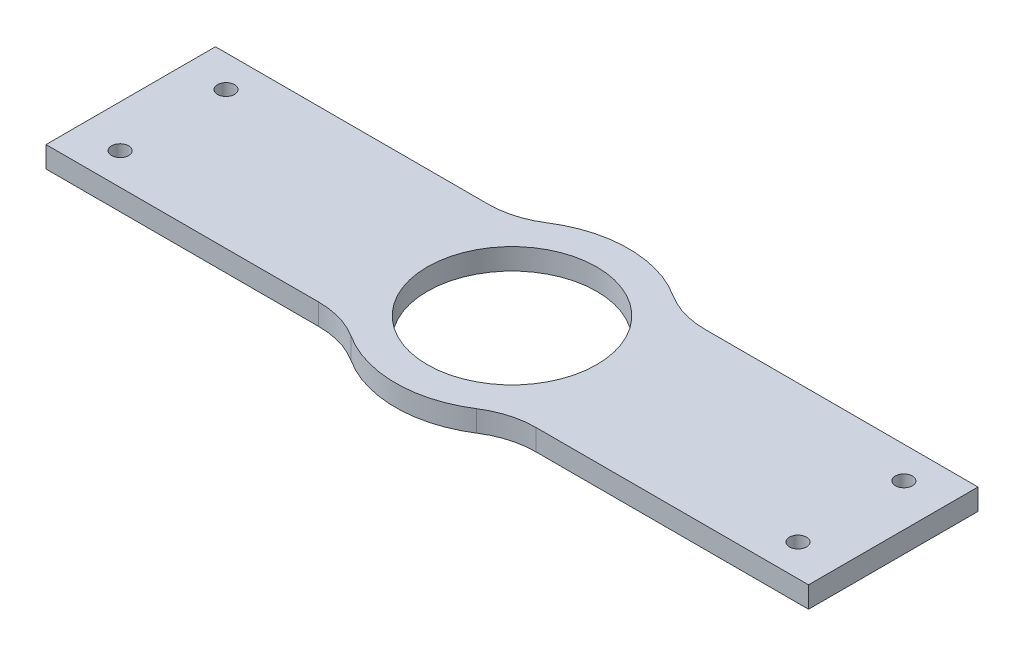
SolidWorks part; units mm, degrees
material "6061-T6 (SS)"
ref_plane "Front" through (0, 0, 0) normal (0, 0, 1) x (1, 0, 0)
ref_plane "Top" through (0, 0, 0) normal (0, 1, 0) x (1, 0, 0)
ref_plane "Right" through (0, 0, 0) normal (1, 0, 0) x (0, 0, -1)
sketch "Sketch1" plane through (0, 0, 0) normal (0, 1, 0) x (1, 0, 0)
  line L0 (228.6, 0) -> (228.6, 19.05) construction
  line L1 (0, 0) -> (81.7659, 0)
  line L2 (0, 0) -> (0, 50.8)
  line L3 (0, 50.8) -> (81.7659, 50.8)
  line L4 (228.6, 0) -> (228.6, 50.8)
  line L5 (0, 50.8) -> (228.6, 0) construction
  line L6 (146.8341, 50.8) -> (228.6, 50.8)
  line L7 (146.8341, 0) -> (228.6, 0)
  arc A0 (95.4645, -4.0105) -> (133.1355, -4.0105) centre (114.3, 25.4) ccw
  arc A1 (133.1355, 54.8105) -> (95.4645, 54.8105) centre (114.3, 25.4) ccw
  arc A2 (81.7659, 0) -> (95.4645, -4.0105) centre (81.7659, -25.4) cw
  arc A3 (146.8341, 0) -> (133.1355, -4.0105) centre (146.8341, -25.4) ccw
  arc A4 (146.8341, 50.8) -> (133.1355, 54.8105) centre (146.8341, 76.2) cw
  arc A5 (81.7659, 50.8) -> (95.4645, 54.8105) centre (81.7659, 76.2) ccw
  point P18 (138.2707, 50.8)
  dimension "D2" = 69.85
  dimension "D3" = 25.4
  dimension "D1" = 50.8
extrude "Boss-Extrude1" add sketch "Sketch1" along normal blind 6.35
sketch "Sketch4" plane through (0, 6.35, 0) normal (0, 1, 0) x (1, 0, 0)
  line L0 (0, 0) -> (12.7, 9.525) construction
  line L1 (0, 0) -> (81.7659, 0) construction
  line L6 (12.7, 9.525) -> (12.7, 41.275) construction
  line L7 (12.7, 41.275) -> (25.4, 50.8) construction
  line L8 (81.7659, 50.8) -> (0, 50.8) construction
  line L9 (114.3, 0) -> (114.3, 25.4) construction
  arc A0 (95.4645, -4.0105) -> (133.1355, -4.0105) centre (114.3, 25.4) ccw construction
  point P0 (12.7, 41.275)
  point P4 (12.7, 9.525)
  point P34 (215.9, 9.525)
  point P36 (215.9, 41.275)
  point P38 (0, 0)
  point P39 (0, 0)
  dimension "D1" = 31.75
  dimension "D2" = 25.4
hole_wizard "#10 Clearance Hole1" positions "Sketch4" profile "Sketch3" hole size "#10" standard "ANSI Inch" end condition up to next
sketch "Sketch3" plane through (12.7, 6.35, -41.275) normal (1, 0, 0) x (0, 0, 1)
  line L0 (0, 0) -> (0, 6.35)
  line L1 (0, 6.35) -> (2.5527, 6.35)
  line L2 (2.5527, 6.35) -> (2.5527, 0)
  line L5 (2.5527, 0) -> (0, 0)
  line L11 (0, -6.35) -> (0, 107.95) construction
  dimension "Thru Hole Dia." = 5.1054
  dimension "Thru Hole Depth" = 6.35
sketch "Sketch5" plane through (0, 6.35, 0) normal (0, 1, 0) x (1, 0, 0)
  circle A0 centre (114.3, 25.4) radius 25.4
  arc A1 (133.1355, 54.8105) -> (95.4645, 54.8105) centre (114.3, 25.4) ccw construction
  dimension "D1" = 50.8
extrude "Cut-Extrude1" cut sketch "Sketch5" against normal through all
